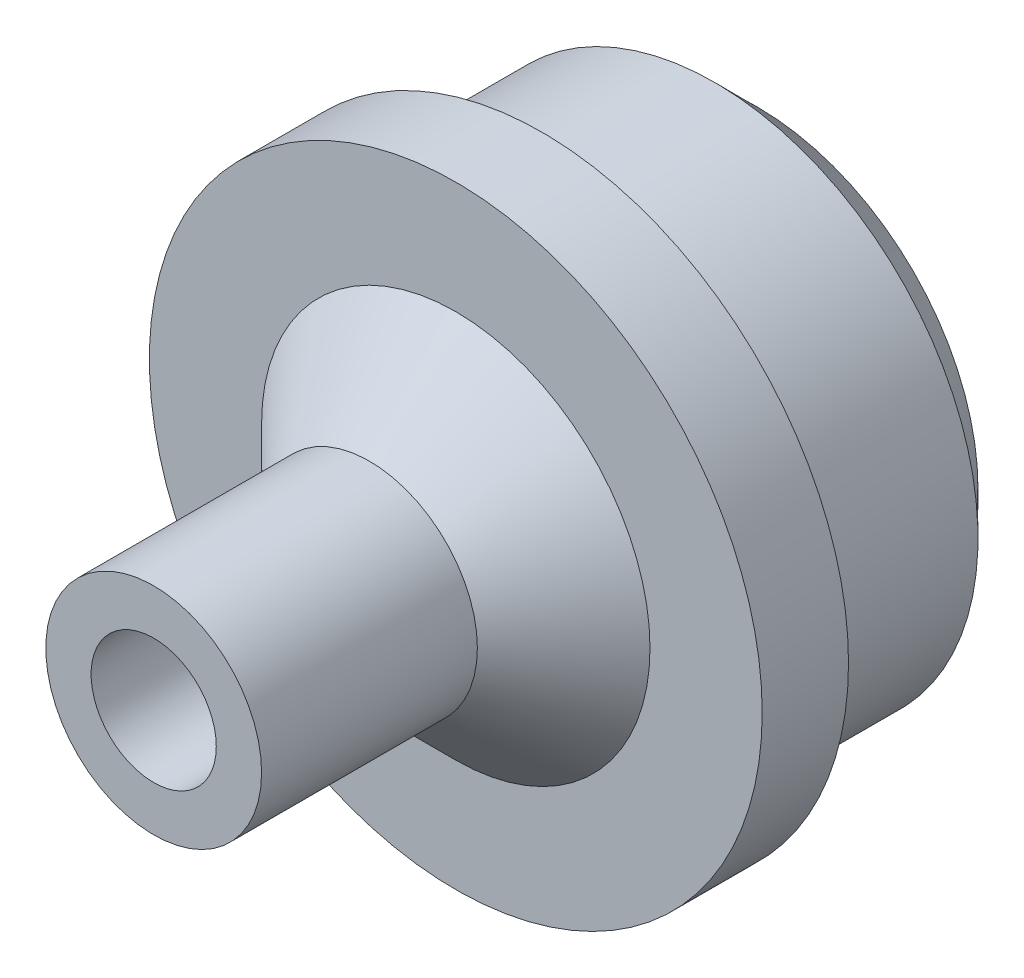
SolidWorks part; units mm, degrees
ref_plane "正面" through (0, 0, 0) normal (0, 0, 1) x (1, 0, 0)
ref_plane "平面" through (0, 0, 0) normal (0, 1, 0) x (1, 0, 0)
ref_plane "右側面" through (0, 0, 0) normal (1, 0, 0) x (0, 0, -1)
sketch "ｽｹｯﾁ1" plane through (0, 0, 0) normal (0, 0, 1) x (1, 0, 0)
  line L3 (-6.0369, 0.875) -> (-6.35, 0.875)
  line L4 (-6.35, -0.875) -> (-6.0369, -0.875)
  line L5 (-6.35, 0.875) -> (-6.35, -0.875)
  line L6 (-6.0369, 0.875) -> (-6.35, 0.875)
  line L7 (-6.35, -0.875) -> (-6.0369, -0.875)
  line L8 (-6.35, 0.875) -> (-6.35, -0.875)
  circle A1 centre (0, 0) radius 7.1
  circle A2 centre (0, 0) radius 7.1
  arc A3 (-6.0369, -0.875) -> (-6.0369, 0.875) centre (0, 0) ccw
  arc A4 (-6.0369, -0.875) -> (-6.0369, 0.875) centre (0, 0) ccw
  dimension "D1" = 0
  dimension "D2" = 0
extrude "ﾎﾞｽ - 押し出し1" add sketch "ｽｹｯﾁ1" against normal blind 5 contours L7 A4 L6 L8 region at (-0.0251, 0, 0)
sketch "ｽｹｯﾁ2" plane through (0, 0, 0) normal (0, 0, 1) x (1, 0, 0)
  circle A1 centre (0, 0) radius 7.1
  circle A2 centre (0, 0) radius 7.1
  dimension "D1" = 0
extrude "ﾎﾞｽ - 押し出し2" add sketch "ｽｹｯﾁ2" along normal blind 2
sketch "ｽｹｯﾁ3" plane through (0, 0, 2) normal (0, 0, 1) x (1, 0, 0)
  circle A0 centre (0, 0) radius 2.5
  dimension "D1" = 5
extrude "ﾎﾞｽ - 押し出し3" add sketch "ｽｹｯﾁ3" along normal blind 7
chamfer "面取り1" distance 2 angle 45 1 edges at (2.5, 0, 2)
sketch "ｽｹｯﾁ4" plane through (0, 0, 9) normal (0, 0, 1) x (1, 0, 0)
  circle A0 centre (0, 0) radius 1.45
  dimension "D1" = 2.9
extrude "ｶｯﾄ - 押し出し1" cut sketch "ｽｹｯﾁ4" against normal blind 30
chamfer "面取り2" distance 1 angle 45 1 edges at (6.1, 0, -5)
